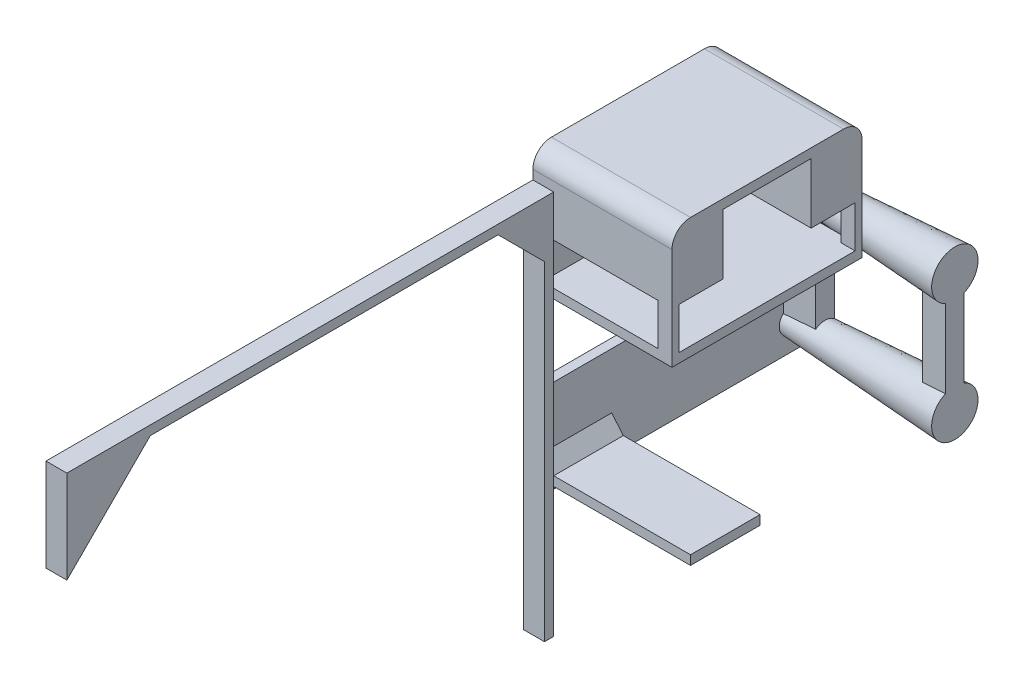
SolidWorks part; units mm, degrees
ref_plane "Front Plane" through (0, 0, 0) normal (0, 0, 1) x (1, 0, 0)
ref_plane "Top Plane" through (0, 0, 0) normal (0, 1, 0) x (1, 0, 0)
ref_plane "Right Plane" through (0, 0, 0) normal (1, 0, 0) x (0, 0, -1)
sketch "Sketch6" plane through (0, 0, 0) normal (1, 0, 0) x (0, 0, -1)
  line L1 (0, 0) -> (105, 0)
  line L2 (0, 0) -> (0, -83)
  line L3 (0, -83) -> (105, -83)
  line L4 (105, 0) -> (105, -83)
  dimension "D1" = 105
  dimension "D2" = 83
extrude "Boss-Extrude3" add sketch "Sketch6" along normal blind 4.5
sketch "Sketch9" plane through (0, -83, 0) normal (0, -1, 0) x (1, 0, 0)
  line L0 (4.5, 0) -> (4.5, -105) construction
  line L1 (0, 0) -> (0, -105) construction
  line L2 (4.5, -2) -> (1.5, -2)
  line L3 (4.5, -2) -> (4.5, -103)
  line L4 (4.5, -103) -> (1.5, -103)
  line L5 (1.5, -2) -> (1.5, -103)
  line L6 (4.5, 0) -> (0, 0) construction
  line L7 (4.5, -105) -> (0, -105) construction
  dimension "D1" = 1.5
  dimension "D2" = 2
  dimension "D3" = 2
extrude "Cut-Extrude6" cut sketch "Sketch9" against normal blind 81
sketch "Sketch10" plane through (0, 0, -2) normal (0, 0, -1) x (-1, 0, 0)
  line L1 (-4.5, -2) -> (-3.5, -2)
  line L2 (-4.5, -2) -> (-4.5, -10)
  line L3 (-4.5, -10) -> (-3.5, -10)
  line L4 (-3.5, -2) -> (-3.5, -10)
  dimension "D1" = 1
  dimension "D2" = 8
extrude "Boss-Extrude4" add sketch "Sketch10" along normal blind 8
sketch "Sketch11" plane through (0, 0, -103) normal (0, 0, 1) x (1, 0, 0)
  line L1 (4.5, -2) -> (3.5, -2)
  line L2 (4.5, -2) -> (4.5, -7)
  line L3 (4.5, -7) -> (3.5, -7)
  line L4 (3.5, -2) -> (3.5, -7)
  dimension "D1" = 5
  dimension "D2" = 1
extrude "Boss-Extrude5" add sketch "Sketch11" along normal blind 5
sketch "Sketch18" plane through (4.5, 0, 0) normal (1, 0, 0) x (0, 0, -1)
  line L0 (103, -12) -> (93, -2)
  line L1 (103, -7) -> (103, -83) construction
  line L2 (98, -2) -> (10, -2) construction
  line L3 (103, -12) -> (103, -2)
  line L4 (103, -2) -> (93, -2)
  line L5 (18, -2) -> (2, -2)
  line L6 (2, -2) -> (2, -18)
  line L7 (2, -10) -> (2, -83) construction
  line L8 (2, -18) -> (18, -2)
  dimension "D1" = 0
  dimension "D2" = 10
  dimension "D3" = 0
  dimension "D4" = 16
  dimension "D5" = 22.6274
extrude "Boss-Extrude12" add sketch "Sketch18" against normal up to vertex (1 mm away) up to point (3.5, -7, -98)
sketch "Sketch27" plane through (0, 0, 0) normal (-1, 0, 0) x (0, 0, 1)
  line L0 (-105, -83) -> (-105, 0) construction
  line L1 (-105, -55) -> (-120, -55)
  line L2 (-105, -55) -> (-105, -53)
  line L3 (-105, -53) -> (-120, -53)
  line L4 (-120, -55) -> (-120, -53)
  line L5 (-125.5, -18) -> (-125.5, 21.7068) construction
  line L6 (-105, -20) -> (-146, -20)
  line L7 (-105, -20) -> (-105, -18)
  line L8 (-105, -18) -> (-146, -18)
  line L9 (-146, -20) -> (-146, -18)
  line L10 (-105, -9) -> (-116, -9)
  line L11 (-105, -9) -> (-105, 6)
  line L12 (-105, 6) -> (-116, 6)
  line L13 (-116, -9) -> (-116, 6)
  line L14 (-146, 6) -> (-135, 6)
  line L15 (-135, -9) -> (-135, 6)
  line L16 (-146, -9) -> (-135, -9)
  line L17 (-146, -9) -> (-146, 6)
  dimension "D1" = 15
  dimension "D2" = 28
  dimension "D3" = 63
  dimension "D4" = 41
  dimension "D5" = 2
  dimension "D6" = 2
  dimension "D7" = 9
  dimension "D8" = 15
  dimension "D9" = 11
extrude "Boss-Extrude20" add sketch "Sketch27" against normal blind 30
sketch "Sketch28" plane through (30, 0, 0) normal (1, 0, 0) x (0, 0, -1)
  line L0 (146, -9) -> (135, -9) construction
  line L1 (146, -20) -> (144.5, -20)
  line L2 (146, -20) -> (146, -9)
  line L3 (146, -9) -> (144.5, -9)
  line L4 (144.5, -20) -> (144.5, -9)
  line L5 (125.5, -18) -> (125.5, -4.7212) construction
  line L6 (105, -18) -> (146, -18) construction
  line L7 (105, -9) -> (106.5, -9)
  line L8 (106.5, -20) -> (106.5, -9)
  line L9 (105, -20) -> (106.5, -20)
  line L10 (105, -20) -> (105, -9)
  dimension "D1" = 1.5
extrude "Boss-Extrude21" add sketch "Sketch28" against normal blind 3
sketch "Sketch29" plane through (30, 0, 0) normal (1, 0, 0) x (0, 0, -1)
  line L0 (105, -20) -> (105, 6) construction
  line L1 (146, 6) -> (105, 6)
  line L2 (146, 6) -> (146, 4)
  line L3 (146, 4) -> (105, 4)
  line L4 (105, 6) -> (105, 4)
  dimension "D1" = 2
extrude "Boss-Extrude22" add sketch "Sketch29" against normal up to vertex (30 mm away) up to point (0, 6, -105)
sketch "Sketch30" plane through (0, 0, -105) normal (0, 0, -1) x (-1, 0, 0)
  line L0 (0, -83) -> (0, -55) construction
  line L1 (0, -58) -> (-2, -58)
  line L2 (0, -58) -> (0, -20)
  line L3 (0, -20) -> (-2, -20)
  line L4 (-2, -58) -> (-2, -20)
  dimension "D1" = 2
  dimension "D2" = 25
  dimension "D3" = 0
extrude "Boss-Extrude23" add sketch "Sketch30" along normal blind 60
sketch "Sketch31" plane through (2, 0, 0) normal (1, 0, 0) x (0, 0, -1)
  line L0 (165, -58) -> (105, -58) construction
  line L1 (165, -20) -> (165, -58) construction
  line L2 (165, -39) -> (129.1416, -39) construction
  circle A0 centre (159, -52) radius 5
  circle A1 centre (159, -26) radius 5
  dimension "D1" = 10
  dimension "D2" = 6
  dimension "D3" = 6
extrude "Boss-Extrude24" add sketch "Sketch31" along normal blind 35
draft "Draft1" type of draft neutral plane draft angle 3.5 faces to draft 1 face at (37, -52, -164) neutral plane through (37, -52, -159) neutral plane normal (1, 0, 0) reverse direction yes parameters "D1"=3.5
draft "Draft3" type of draft neutral plane draft angle 3.5 faces to draft 1 face at (37, -26, -154) neutral plane through (37, -26, -159) neutral plane normal (1, 0, 0) reverse direction yes parameters "D1"=3.5
sketch "Sketch32" plane through (2, 0, 0) normal (1, 0, 0) x (0, 0, -1)
  line L1 (161, -53) -> (157, -53)
  line L2 (161, -53) -> (161, -25)
  line L3 (161, -25) -> (157, -25)
  line L4 (157, -53) -> (157, -25)
  circle A0 centre (159, -52) radius 2.8593 construction
  circle A1 centre (159, -26) radius 2.8593 construction
  dimension "D1" = 2
  dimension "D2" = 2
  dimension "D3" = 1
  dimension "D4" = 1
  dimension "D5" = 2
extrude "Boss-Extrude25" add sketch "Sketch32" along normal blind 7
sketch "Sketch33" plane through (37, 0, 0) normal (1, 0, 0) x (0, 0, -1)
  line L1 (157, -26) -> (161, -26)
  line L2 (157, -26) -> (157, -52)
  line L3 (157, -52) -> (161, -52)
  line L4 (161, -26) -> (161, -52)
  circle A0 centre (159, -26) radius 5 construction
  circle A1 centre (159, -52) radius 5 construction
  point P6 (159, -26)
  dimension "D1" = 0
  dimension "D2" = 4
  dimension "D3" = 0
  dimension "D4" = 0
extrude "Boss-Extrude26" add sketch "Sketch33" against normal blind 5
sketch "Sketch39" plane through (0, 0, 0) normal (-1, 0, 0) x (0, 0, 1)
  line L0 (-105, -18) -> (-105, -9) construction
  line L1 (-146, 6) -> (-105, 6)
  line L2 (-146, 6) -> (-146, -18)
  line L3 (-146, -18) -> (-105, -18)
  line L4 (-105, 6) -> (-105, -18)
  line L5 (-105, -18) -> (-146, -18) construction
  dimension "D1" = 0
  dimension "D2" = 0
extrude "Boss-Extrude30" add sketch "Sketch39" against normal blind 2
sketch "Sketch40" plane through (2, 0, 0) normal (1, 0, 0) x (0, 0, -1)
  line L1 (116, 4) -> (135, 4) construction
  line L2 (116, -9) -> (116, 4) construction
  circle A0 centre (125.5, -6.5) radius 5
  point P4 (125.5, 4)
  point P7 (116, -2.5)
  dimension "D1" = 0
  dimension "D2" = 4
  dimension "D3" = 10
extrude "Cut-Extrude9" cut sketch "Sketch40" against normal blind 2
sketch "Sketch41" plane through (0, 0, -120) normal (0, 0, -1) x (-1, 0, 0)
  line L0 (-2, -54) -> (-7.9406, -54) construction
  line L1 (-2, -55) -> (-2, -53) construction
  line L2 (-2, -55) -> (-2, -58)
  line L3 (-2, -58) -> (-4.5, -55)
  line L4 (-30, -55) -> (-2, -55) construction
  line L5 (-4.5, -55) -> (-2, -55)
  line L7 (-2, -50) -> (-4.5, -53)
  line L8 (-2, -53) -> (-2, -50)
  line L9 (-4.5, -53) -> (-2, -53)
  dimension "D1" = 0
  dimension "D2" = 0
extrude "Boss-Extrude31" add sketch "Sketch41" along direction (0, 0, 1) on the side against the normal up to surface (15 mm away) up to face at (2.1667, -65.3333, -105)
sketch "Sketch42" plane through (30, 0, 0) normal (1, 0, 0) x (0, 0, -1)
  line L1 (105, -55) -> (120, -55)
  line L2 (105, -55) -> (105, -53)
  line L3 (105, -53) -> (120, -53)
  line L4 (120, -55) -> (120, -53)
extrude "Boss-Extrude32" add sketch "Sketch42" along normal blind 4
sketch "Sketch45" plane through (2, 0, 0) normal (1, 0, 0) x (0, 0, -1)
  line L0 (165, -58) -> (120, -58) construction
  line L1 (105, -20) -> (135, -20)
  line L2 (105, -20) -> (105, -38)
  line L3 (105, -38) -> (135, -38)
  line L4 (135, -20) -> (135, -38)
  line L5 (165, -20) -> (165, -58) construction
  dimension "D1" = 20
  dimension "D2" = 30
extrude "Cut-Extrude10" cut sketch "Sketch45" against normal blind 5
fillet "Fillet1" radius 4 1 edges at (15, 6, -146)
fillet "Fillet2" radius 4 1 edges at (15, 6, -105)
sketch "Sketch46" plane through (4.5, 0, 0) normal (1, 0, 0) x (0, 0, -1)
  line L0 (18, -2) -> (0, -20)
  line L1 (0, 0) -> (0, -83) construction
  line L2 (0, -20) -> (0, -83)
  line L3 (0, -83) -> (103, -83)
  line L4 (103, -83) -> (103, -12)
  line L5 (103, -12) -> (93, -2)
  line L6 (93, -2) -> (18, -2)
extrude "Cut-Extrude11" cut sketch "Sketch46" against normal blind 10
sketch "Sketch47" plane through (1.5, 0, 0) normal (1, 0, 0) x (0, 0, -1)
  line L0 (93, -2) -> (103, -2)
  line L1 (103, -2) -> (103, -12)
  line L2 (103, -12) -> (93, -2)
  line L3 (2, -18) -> (18, -2)
  line L4 (18, -2) -> (2, -2)
  line L5 (2, -2) -> (18, -2) construction
  line L6 (2, -2) -> (2, -18) construction
  line L7 (2, -2) -> (2, -18)
extrude "Cut-Extrude12" cut sketch "Sketch47" against normal blind 0.5
